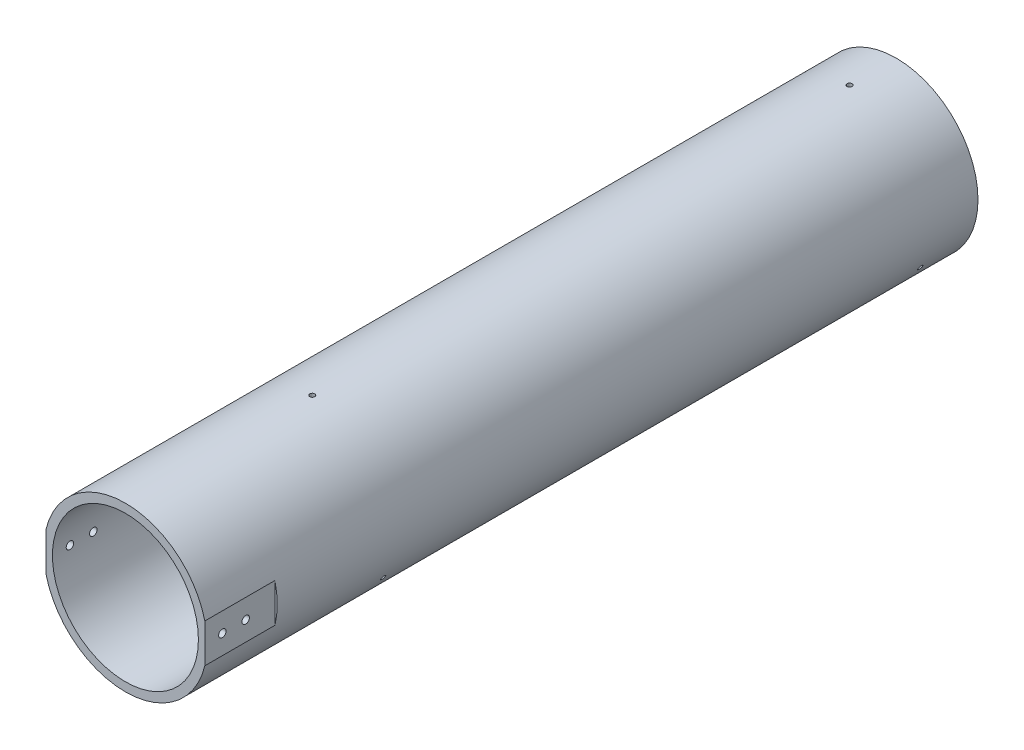
SolidWorks part; units mm, degrees
ref_plane "Front Plane" through (0, 0, 0) normal (0, 0, 1) x (1, 0, 0)
ref_plane "Top Plane" through (0, 0, 0) normal (0, 1, 0) x (1, 0, 0)
ref_plane "Right Plane" through (0, 0, 0) normal (1, 0, 0) x (0, 0, -1)
sketch "Sketch1" plane through (0, 0, 0) normal (0, 0, 1) x (1, 0, 0)
  circle A0 centre (0, 0) radius 39.6875
  circle A1 centre (0, 0) radius 44.45
  dimension "D1" = 88.9
  dimension "D2" = 79.375
extrude "Boss-Extrude1" add sketch "Sketch1" along normal mid plane 419.1
sketch "Sketch2" plane through (0, 0, 209.55) normal (0, 0, 1) x (1, 0, 0)
  line L1 (43.18, 13.8246) -> (51.0798, 13.8246)
  line L2 (43.18, 13.8246) -> (43.18, -14.6378)
  line L3 (43.18, -14.6378) -> (51.0798, -14.6378)
  line L4 (51.0798, 13.8246) -> (51.0798, -14.6378)
  dimension "D1" = 43.18
extrude "Cut-Extrude1" cut sketch "Sketch2" against normal blind 38.1
hole_wizard "#10-32 Tapped Hole1" positions "Sketch4" profile "Sketch3" tap size "#10-32" standard "ANSI Inch"
sketch "Sketch4" plane through (43.18, 0, 0) normal (1, 0, 0) x (0, 0, -1)
  line L0 (-209.55, 10.5494) -> (-209.55, -10.5494) construction
  point P0 (-200.025, 0)
  point P2 (-187.325, 0)
  dimension "D1" = 9.525
  dimension "D2" = 12.7
sketch "Sketch3" plane through (43.18, 0, 200.025) normal (0, 1, 0) x (0, 0, -1)
  line L0 (0, 0) -> (0, 14.9293)
  line L1 (0, 14.9293) -> (2.0193, 13.716)
  line L2 (2.0193, 13.716) -> (2.0193, 0)
  line L5 (2.0193, 0) -> (0, 0)
  line L10 (0, 14.9293) -> (-2.0193, 13.716) construction
  line L11 (0, -6.35) -> (0, 107.95) construction
  dimension "Tap Drill Dia." = 4.0386
  dimension "Tap Drill Depth" = 13.716
  dimension "Drill Angle" = 118
cosmetic thread "Hole Thread1" parameters "D1"=5.1335, "D2"=4.826
cosmetic thread "Hole Thread2" parameters "D1"=5.1335, "D2"=4.826
hole_wizard "#6-32 Tapped Hole1" positions "Sketch6" profile "Sketch5" tap size "#6-32" standard "ANSI Inch"
sketch "Sketch6" plane through (0, 0, -209.55) normal (0, 0, -1) x (-1, 0, 0)
  point P0 (0, 42.0688)
  point P2 (-42.0688, 0)
  point P4 (42.0688, 0)
  point P6 (0, -42.0688)
  dimension "D1" = 42.0688
  dimension "D2" = 42.0688
  dimension "D3" = 42.0688
  dimension "D4" = 42.0688
sketch "Sketch5" plane through (0, 42.0688, -209.55) normal (1, 0, 0) x (0, 1, 0)
  line L0 (0, 0) -> (0, 15.7987)
  line L1 (0, 15.7987) -> (1.3525, 14.986)
  line L2 (1.3525, 14.986) -> (1.3525, 0)
  line L5 (1.3525, 0) -> (0, 0)
  line L10 (0, 15.7987) -> (-1.3526, 14.986) construction
  line L11 (0, -6.35) -> (0, 107.95) construction
  dimension "Tap Drill Dia." = 2.7051
  dimension "Tap Drill Depth" = 14.986
  dimension "Drill Angle" = 118
cosmetic thread "Hole Thread3" parameters "D1"=10.922, "D2"=3.5052
cosmetic thread "Hole Thread4" parameters "D1"=10.922, "D2"=3.5052
cosmetic thread "Hole Thread5" parameters "D1"=10.922, "D2"=3.5052
cosmetic thread "Hole Thread6" parameters "D1"=10.922, "D2"=3.5052
mirror "Mirror1" about plane through (0, 0, 0) normal (1, 0, 0) of "#10-32 Tapped Hole1", "Cut-Extrude1"
hole_wizard "#6-32 Tapped Hole2" positions "3DSketch2" profile "Sketch8" tap size "#6-32" standard "ANSI Inch" end condition up to next
sketch3d "3DSketch2"
  point P0 (0, 44.45, -184.15)
  point P2 (0, 44.45, 107.95)
  dimension "D1" = 25.4
  dimension "D2" = 101.6
  dimension "D3" = 0
  dimension "D4" = 0
sketch "Sketch8" plane through (0, 44.45, -184.15) normal (1, 0, 0) x (0, 0, 1)
  line L0 (0, 0) -> (0, 88.9)
  line L1 (0, 88.9) -> (1.3525, 88.9)
  line L2 (1.3525, 88.9) -> (1.3525, 0)
  line L5 (1.3525, 0) -> (0, 0)
  line L11 (0, -6.35) -> (0, 107.95) construction
  dimension "Thru Tap Drill Dia." = 2.7051
  dimension "Thru Tap Drill Depth" = 88.9
cosmetic thread "Hole Thread7" parameters "D2"=3.5052
cosmetic thread "Hole Thread8" parameters "D2"=3.5052
pattern_circular "CirPattern1" count 3 over 360 about axis through (0, 0, -209.55) along (0, 0, 1) of "#6-32 Tapped Hole2"
